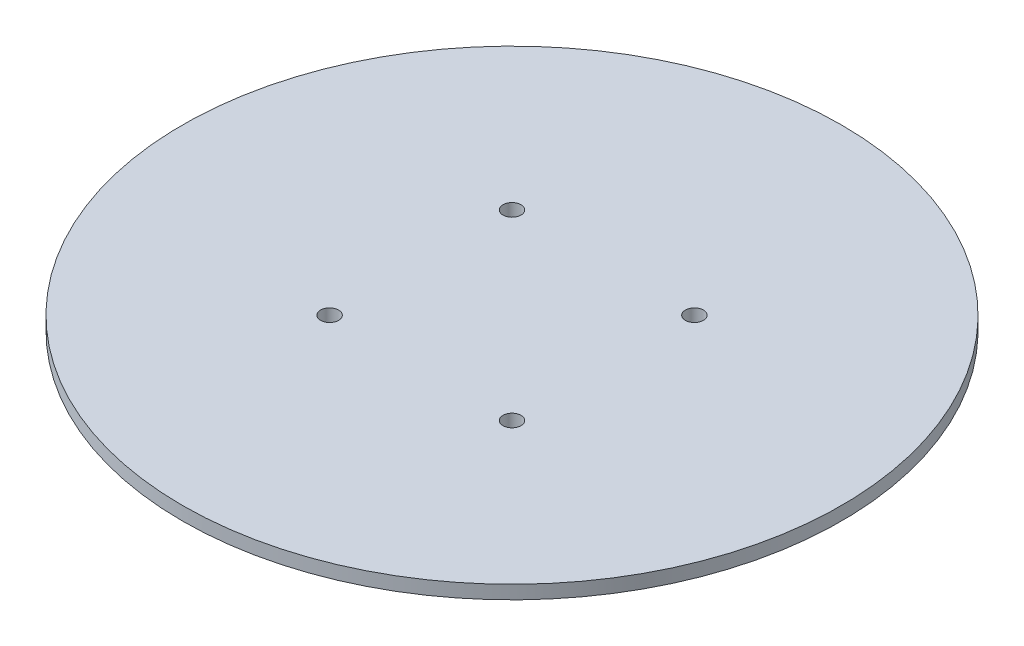
SolidWorks part; units mm, degrees
material "ABS"
ref_plane "Front Plane" through (0, 0, 0) normal (0, 0, 1) x (1, 0, 0)
ref_plane "Top Plane" through (0, 0, 0) normal (0, 1, 0) x (1, 0, 0)
ref_plane "Right Plane" through (0, 0, 0) normal (1, 0, 0) x (0, 0, -1)
sketch "Sketch1" plane through (0, 0, 0) normal (0, 1, 0) x (1, 0, 0)
  line L0 (0, 58.8429) -> (0, 0) construction
  line L1 (0, 0) -> (46.9181, 0) construction
  circle A0 centre (0, 0) radius 73.2
  circle A1 centre (20.2538, 20.2538) radius 20.2538 construction
  circle A2 centre (20.2538, -20.2538) radius 20.2538 construction
  circle A3 centre (-20.2538, -20.2538) radius 20.2538 construction
  circle A4 centre (-20.2538, 20.2538) radius 20.2538 construction
  circle A6 centre (20.2538, 20.2538) radius 2
  circle A9 centre (20.2538, -20.2538) radius 2
  circle A10 centre (-20.2538, -20.2538) radius 2
  circle A11 centre (-20.2538, 20.2538) radius 2
  point P16 (0, 0)
  point P24 (0, 0)
  dimension "D1" = 146.4
  dimension "D3" = 4
  dimension "D2" = 4
  dimension "D4" = 4
extrude "Boss-Extrude1" add sketch "Sketch1" along normal blind 1.5 and the other way blind 1.5
